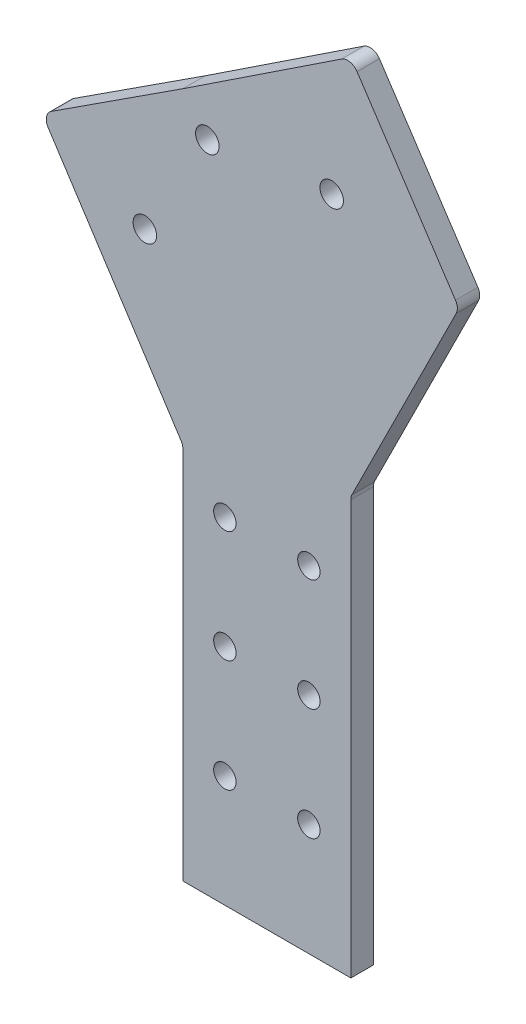
SolidWorks part; units mm, degrees
material "Thornel Mat VMA"
ref_plane "前视基准面" through (0, 0, 0) normal (0, 0, 1) x (1, 0, 0)
ref_plane "上视基准面" through (0, 0, 0) normal (0, 1, 0) x (1, 0, 0)
ref_plane "右视基准面" through (0, 0, 0) normal (1, 0, 0) x (0, 0, -1)
other "Configuration Table"
sketch "草图13" plane through (0, 0, 0) normal (0, 0, 1) x (1, 0, 0)
  line L3 (-30, -100) -> (0, -100)
  line L4 (0, -100) -> (0, 0)
  line L5 (-30, -100) -> (-30, 22.5178)
  line L7 (0, 42.3743) -> (0, 0)
  line L8 (-30, 22.5178) -> (0, 42.3743)
  dimension "D1" = 56.5
  dimension "D4" = 30
extrude "凸台-拉伸1" add sketch "草图13" along normal blind 4
sketch "草图14" plane through (0, 0, 4) normal (0, 0, 1) x (1, 0, 0)
  line L0 (-30, -100) -> (0, -100) construction
  line L1 (-15, -100) -> (-15, -80.3764) construction
  circle A0 centre (-22.5, -40) radius 2
  circle A1 centre (-7.5, -40) radius 2
  circle A2 centre (-7.5, -60) radius 2
  circle A3 centre (-7.5, -80) radius 2
  circle A4 centre (-22.5, -60) radius 2
  circle A5 centre (-22.5, -80) radius 2
  dimension "D1" = 4
  dimension "D2" = 15
  dimension "D3" = 60
  dimension "D4" = 2
  dimension "D5" = 3
extrude "切除-拉伸1" cut sketch "草图14" against normal up to next
sketch "草图16" plane through (0, 0, 4) normal (0, 0, 1) x (1, 0, 0)
  line L0 (-30, 22.5178) -> (-55.1601, 6.1786)
  line L5 (-55.1601, 6.1786) -> (-30, -32.5646)
  line L6 (-30, 22.5178) -> (-30, -100) construction
  line L7 (-30, -32.5646) -> (-30, 22.5178)
extrude "凸台-拉伸2" add sketch "草图16" against normal up to surface (4 mm away) up to face at (-20.5, -60, 0)
sketch "草图17" plane through (0, 0, 4) normal (0, 0, 1) x (1, 0, 0)
  circle A0 centre (-3.4299, 19.4979) radius 2.1
  circle A1 centre (-25.627, 16.798) radius 2.1
  circle A2 centre (-36.7854, -2.5796) radius 2.1
  dimension "D1" = 4.2
  dimension "D2" = 4.2
  dimension "D3" = 4.2
extrude "切除-拉伸2" cut sketch "草图17" against normal blind 10
sketch "草图18" plane through (0, 0, 4) normal (0, 0, 1) x (1, 0, 0)
  line L0 (0, 42.3743) -> (19.3178, 13.1883)
  line L1 (19.3178, 13.1883) -> (0, -25.5572)
  line L2 (0, -100) -> (0, 42.3743) construction
  line L3 (0, 42.3743) -> (0, -25.5572)
  line L4 (0, 42.3743) -> (-30, 22.5178) construction
  dimension "D1" = 35
  dimension "D2" = 120
extrude "凸台-拉伸3" add sketch "草图18" against normal blind 4
fillet "圆角1" radius 2 5 edges at (0, -25.5572, 2) (-30, -32.5646, 2) (-55.1601, 6.1786, 2) (19.3178, 13.1883, 2) (0, 42.3743, 2)
